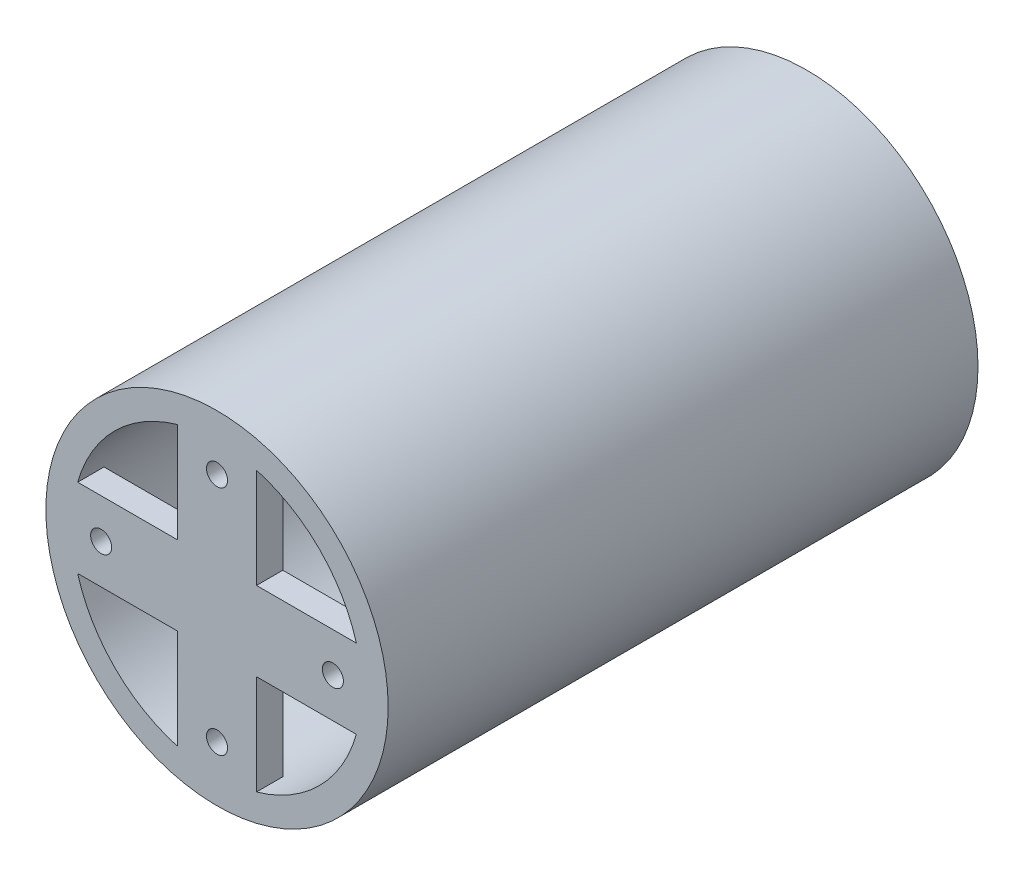
SolidWorks part; units mm, degrees
ref_plane "Alzado" through (0, 0, 0) normal (0, 0, 1) x (1, 0, 0)
ref_plane "Planta" through (0, 0, 0) normal (0, 1, 0) x (1, 0, 0)
ref_plane "Vista lateral" through (0, 0, 0) normal (1, 0, 0) x (0, 0, -1)
sketch "Croquis1" plane through (0, 0, 0) normal (0, 0, 1) x (1, 0, 0)
  circle A0 centre (0, 0) radius 32.5
  circle A1 centre (0, 0) radius 27.5
  dimension "D1" = 65
  dimension "D2" = 5
extrude "Boss-Extrude1" add sketch "Croquis1" along normal blind 112
sketch "Sketch1" plane through (0, 0, 0) normal (0, 0, -1) x (-1, 0, 0)
  line L0 (0, 0) -> (11.3818, 0) construction
  circle A0 centre (-30, 0) radius 1.5
  circle A1 centre (0, 30) radius 1.5
  circle A2 centre (30, 0) radius 1.5
  circle A3 centre (0, -30) radius 1.5
  circle A7 centre (0, 0) radius 30 construction
  circle A8 centre (0, 0) radius 27.5 construction
  point P17 (0, 0)
  dimension "D1" = 2.5
  dimension "D2" = 3
  dimension "D3" = 0
  dimension "D4" = 4
extrude "Cut-Extrude1" cut sketch "Sketch1" against normal blind 5
sketch "Sketch2" plane through (0, 0, 112) normal (0, 0, 1) x (1, 0, 0)
  line L0 (-30, 7.5) -> (-30, -7.5)
  line L1 (-30, -7.5) -> (-7.5, -7.5)
  line L2 (-7.5, -7.5) -> (-7.5, -30)
  line L3 (-7.5, -30) -> (7.5, -30)
  line L4 (7.5, -30) -> (7.5, -7.5)
  line L5 (7.5, -7.5) -> (30, -7.5)
  line L6 (30, -7.5) -> (30, 7.5)
  line L7 (30, 7.5) -> (7.5, 7.5)
  line L8 (7.5, 7.5) -> (7.5, 30)
  line L9 (7.5, 30) -> (-7.5, 30)
  line L10 (-7.5, 30) -> (-7.5, 7.5)
  line L11 (-7.5, 7.5) -> (-30, 7.5)
  circle A0 centre (-22, 0) radius 2
  circle A2 centre (0, 22) radius 2
  circle A3 centre (22, 0) radius 2
  circle A4 centre (0, -22) radius 2
  point P6 (-30, 0)
  point P15 (30, 0)
  point P17 (0, 30)
  point P18 (0, -30)
  point P28 (0, 0)
  dimension "D6" = 4
  dimension "D1" = 15
  dimension "D2" = 15
  dimension "D3" = 60
  dimension "D4" = 60
  dimension "D5" = 22
  dimension "D7" = 4
extrude "Boss-Extrude2" add sketch "Sketch2" against normal blind 5
